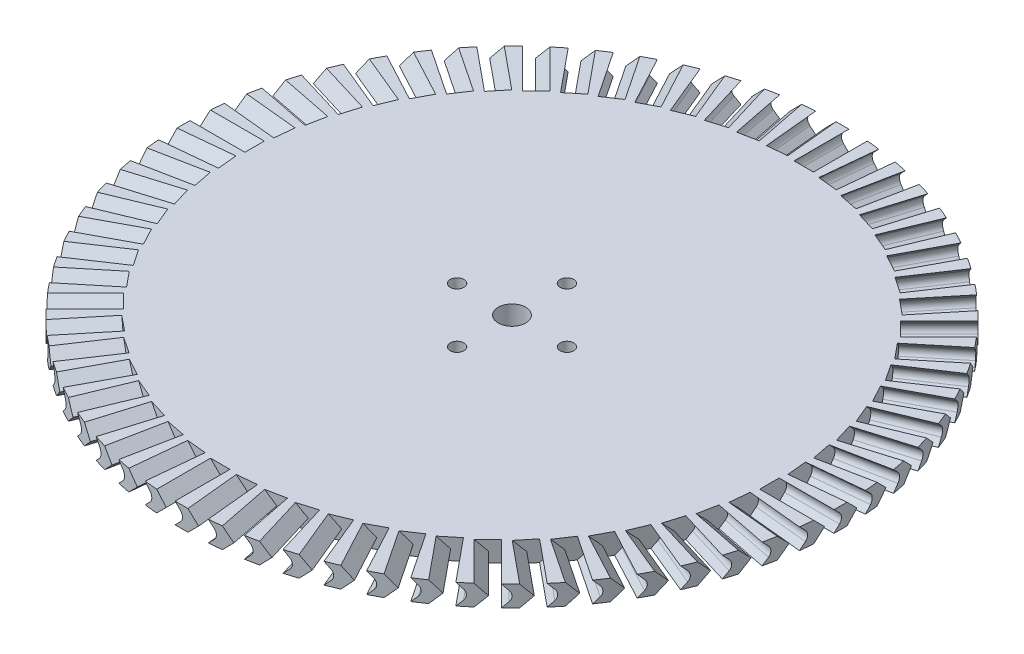
SolidWorks part; units mm, degrees
material "AISI 316 Annealed Stainless Steel Bar (SS)"
ref_plane "Front Plane" through (0, 0, 0) normal (0, 0, 1) x (1, 0, 0)
ref_plane "Top Plane" through (0, 0, 0) normal (0, 1, 0) x (1, 0, 0)
ref_plane "Right Plane" through (0, 0, 0) normal (1, 0, 0) x (0, 0, -1)
sketch "Sketch1" plane through (0, 0, 0) normal (0, 1, 0) x (1, 0, 0)
  circle A0 centre (0, 0) radius 6.35
  circle A1 centre (0, 0) radius 152.4
  circle A2 centre (0, 25.4) radius 3.175
  circle A3 centre (25.4, 0) radius 3.175
  circle A4 centre (0, -25.4) radius 3.175
  circle A5 centre (-25.4, 0) radius 3.175
  point P6 (-9.0629, -29.4221)
  point P7 (0, 0)
  point P15 (0, 0)
  dimension "D1" = 12.7
  dimension "D2" = 304.8
  dimension "D3" = 6.35
  dimension "D4" = 25.4
  dimension "D5" = 4
extrude "Boss-Extrude1" add sketch "Sketch1" along normal blind 9.525
ref_plane "Plane1" through (0, 0, 152.4) normal (0, 0, 1) x (1, 0, 0)
sketch "Sketch2" plane through (0, 0, 152.4) normal (0, 0, 1) x (1, 0, 0)
  line L4 (-0.9299, 2.5174) -> (-3.4474, 0)
  line L5 (-152.4, 0) -> (152.4, 0) construction
  line L6 (-0.9299, 7.0076) -> (-3.4474, 9.525)
  line L9 (152.4, 9.525) -> (-152.4, 9.525) construction
  line L10 (-5.4201, 2.5174) -> (-12.4276, 9.525)
  line L11 (-5.4201, 7.0076) -> (-12.4276, 0)
  line L12 (-12.4276, 9.525) -> (-3.4474, 9.525)
  line L13 (-12.4276, 0) -> (-3.4474, 0)
  line L14 (0, 0) -> (0, 9.525) construction
  line L15 (6.35, 9.525) -> (-6.35, 9.525) construction
  line L16 (-3.175, 4.7625) -> (0, 4.7625) construction
  circle A0 centre (-3.175, 4.7625) radius 3.175
  point P19 (0, 4.7625)
  point P21 (-13.8299, 0)
  point P22 (-12.4276, 9.525)
  point P23 (-6.2899, 4.1474)
  dimension "D1" = 6.35
  dimension "D2" = 45
  dimension "D3" = 45
extrude "Cut-Extrude1" cut sketch "Sketch2" against normal blind 25.4 contours A0 | A0 L6 L12 L10 L11 | A0 L11 L10 | A0 L10 L11 L13 L4 region at (-7.2864, 1.5647, 152.4) region at (-3.175, 4.7625, 152.4) region at (-6.6622, 4.7625, 152.4) region at (-7.2864, 7.9603, 152.4)
pattern_circular "CirPattern1" count 64 over 360 about axis through (0, 9.525, 0) along (0, -1, 0) of "Cut-Extrude1" reverse direction yes
